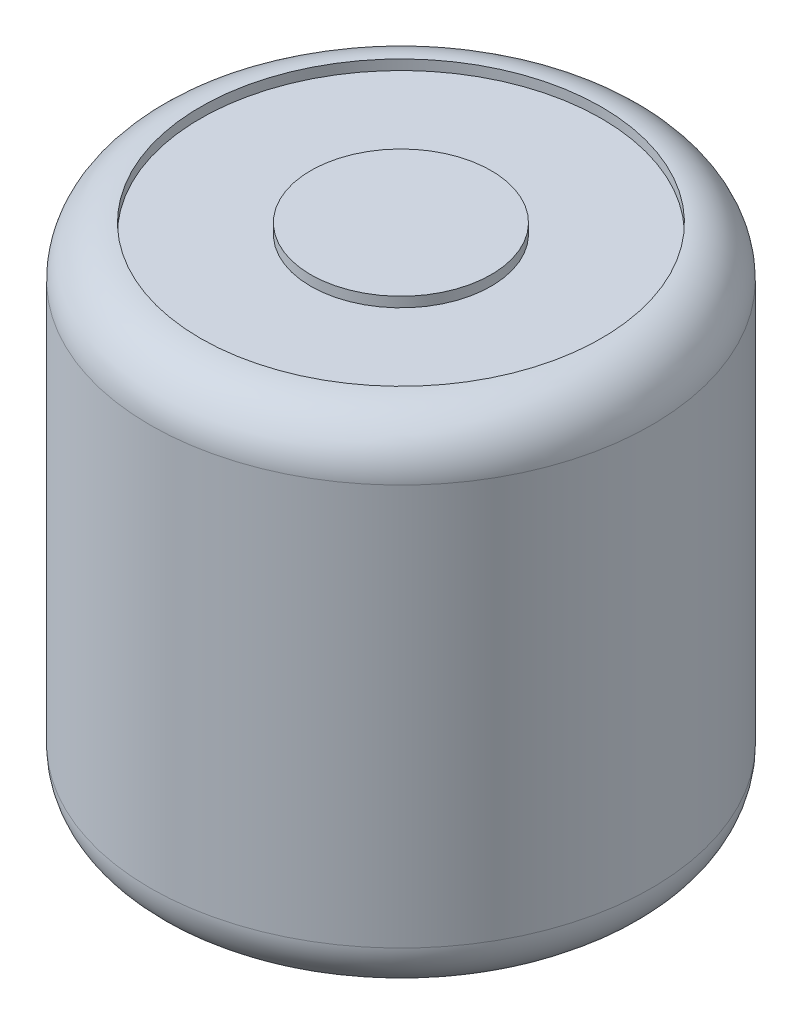
SolidWorks part; units mm, degrees
material "AISI 1020 Steel, Cold Rolled"
ref_plane "Front Plane" through (0, 0, 0) normal (0, 0, 1) x (1, 0, 0)
ref_plane "Top Plane" through (0, 0, 0) normal (0, 1, 0) x (1, 0, 0)
ref_plane "Right Plane" through (0, 0, 0) normal (1, 0, 0) x (0, 0, -1)
sketch "Sketch1" plane through (0, 0, 0) normal (0, 1, 0) x (1, 0, 0)
  circle A0 centre (0, 0) radius 5
  dimension "D1" = 10
extrude "Boss-Extrude1" add sketch "Sketch1" along normal blind 10
sketch "Sketch2" plane through (0, 10, 0) normal (0, 1, 0) x (1, 0, 0)
  circle A0 centre (0, 0) radius 4
  circle A1 centre (0, 0) radius 1.8
  dimension "D1" = 8
  dimension "D2" = 3.6
extrude "Cut-Extrude1" cut sketch "Sketch2" against normal blind 0.2
fillet "Fillet1" radius 1 2 edges at (0, 10, 5) (0, 0, 5)
sketch "Sketch3" plane through (0, 0, 0) normal (0, -1, 0) x (1, 0, 0)
  circle A0 centre (0, 0) radius 1
  dimension "D1" = 2
extrude "Cut-Extrude2" cut sketch "Sketch3" against normal blind 3
